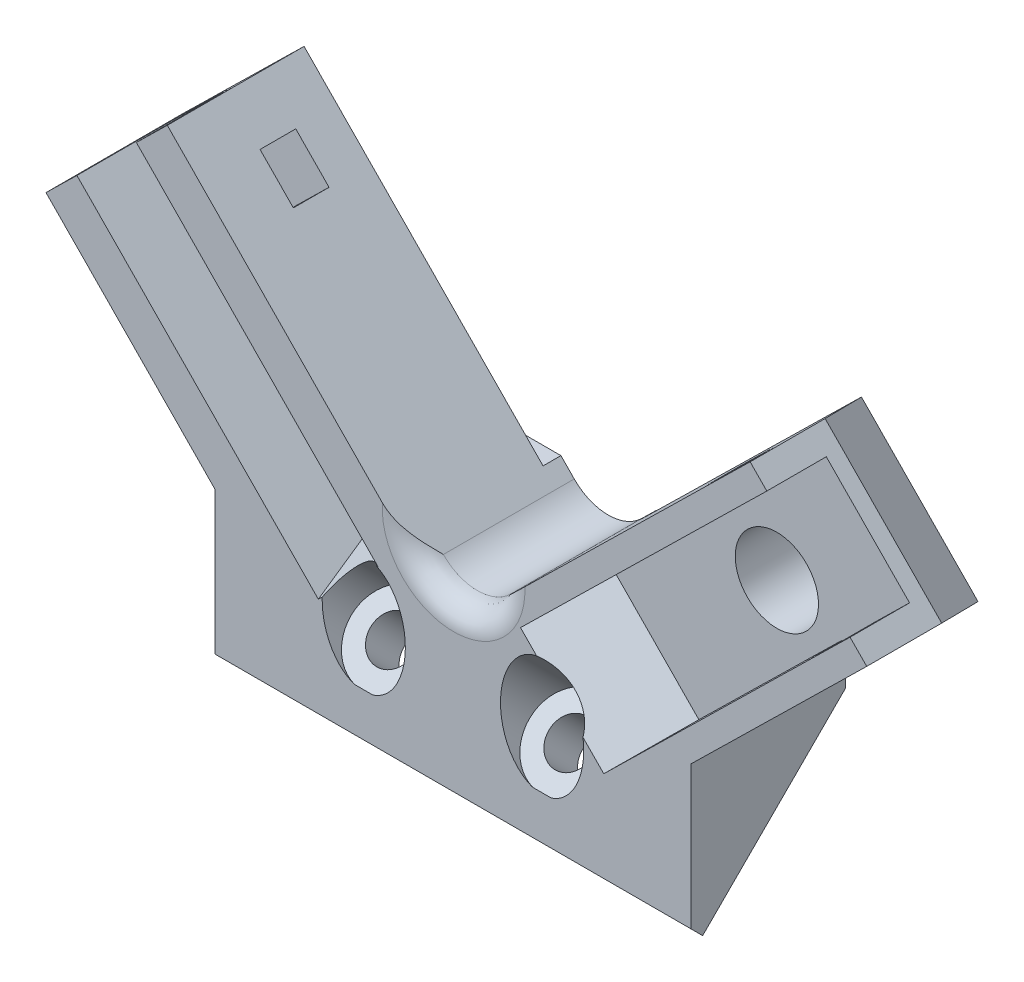
SolidWorks part; units mm, degrees
ref_plane "Plan de face" through (0, 0, 0) normal (0, 0, 1) x (1, 0, 0)
ref_plane "Plan de dessus" through (0, 0, 0) normal (0, 1, 0) x (1, 0, 0)
ref_plane "Plan de droite" through (0, 0, 0) normal (1, 0, 0) x (0, 0, -1)
sketch "Esquisse1" plane through (0, 0, 0) normal (0, 0, 1) x (1, 0, 0)
  line L0 (-20, 0) -> (20, 0)
  line L1 (20, 0) -> (20, 8)
  line L2 (20, 8) -> (34.795, 22.502)
  line L3 (34.795, 22.502) -> (24.995, 32.5)
  line L4 (24.995, 32.5) -> (0, 8)
  line L5 (0, 8) -> (-24.0148, 32.5)
  line L6 (-24.0148, 32.5) -> (-34.2148, 22.502)
  line L7 (-34.2148, 22.502) -> (-20, 8)
  line L8 (-20, 8) -> (-20, 0)
  line L9 (26.3936, 8) -> (-28.5359, 8) construction
  line L10 (0, -5.9689) -> (0, 32.3975) construction
  line L11 (-27.4321, 32.5) -> (31.9826, 32.5) construction
  line L12 (-36.6901, 22.502) -> (47.9026, 22.502) construction
  dimension "D1" = 40
  dimension "D2" = 14
  dimension "D3" = 35
  dimension "D4" = 8
extrude "Boss.-Extru.1" add sketch "Esquisse1" along normal blind 15
sketch "Esquisse2" plane through (0, 0, 15) normal (0, 0, 1) x (1, 0, 0)
  line L0 (26.395, 31.0717) -> (13.5404, 18.4717)
  line L1 (34.795, 22.502) -> (24.995, 32.5) construction
  line L2 (13.5404, 18.4717) -> (20.5404, 11.3303)
  line L3 (20.5404, 11.3303) -> (33.395, 23.9303)
  line L4 (33.395, 23.9303) -> (26.395, 31.0717)
  line L5 (26.8028, 24.47) -> (8.3585, 6.391) construction
  dimension "D1" = 18
  dimension "D2" = 10
extrude "Enlèv. mat.-Extru.1" cut sketch "Esquisse2" against normal blind 5
sketch "Esquisse3" plane through (0, 0, 15) normal (0, 0, 1) x (1, 0, 0)
  line L0 (-26.5529, 24.8874) -> (-10.8337, 8.8505) construction
  line L1 (-31.6143, 25.051) -> (-19.0143, 12.1964)
  line L2 (-19.0143, 12.1964) -> (-14.0153, 17.0964)
  line L3 (-14.0153, 17.0964) -> (-26.6153, 29.951)
  line L4 (-26.6153, 29.951) -> (-31.6143, 25.051)
  line L5 (-24.0148, 32.5) -> (-34.2148, 22.502) construction
  dimension "D1" = 7
  dimension "D2" = 18
extrude "Enlèv. mat.-Extru.2" cut sketch "Esquisse3" against normal blind 8
chamfer "Chanfrein1" distance 11 angle 50 1 edges at (17.0404, 14.901, 15) first distance on face at (0.2454, 17.8296, 15)
sketch "Esquisse8" plane through (-6.2008, -6.078, 0) normal (-0.7141, -0.7, 0) x (0, 0, 1)
  line L0 (7, 40.02) -> (7, 22.02) construction
  line L1 (7, 36.02) -> (10, 36.02)
  line L2 (7, 36.02) -> (7, 32.02)
  line L3 (7, 32.02) -> (10, 32.02)
  line L4 (10, 36.02) -> (10, 32.02)
  line L5 (15, 40.02) -> (0, 40.02) construction
  dimension "D1" = 4
  dimension "D2" = 4
  dimension "D3" = 3
extrude "Enlèv. mat.-Extru.6" cut sketch "Esquisse8" against normal blind 50
sketch "Esquisse7" plane through (5.8008, -5.918, 0) normal (0.7, -0.7141, 0) x (0.7141, 0.7, 0)
  line L0 (15.7955, 10) -> (40.6, 10) construction
  line L1 (32.6, 10) -> (36.6, 10)
  line L2 (32.6, 10) -> (32.6, 13)
  line L3 (32.6, 13) -> (36.6, 13)
  line L4 (36.6, 10) -> (36.6, 13)
  line L6 (40.6, 15) -> (40.6, 0) construction
  dimension "D1" = 4
  dimension "D2" = 4
  dimension "D3" = 3
extrude "Enlèv. mat.-Extru.5" cut sketch "Esquisse7" against normal blind 50
sketch "Esquisse6" plane through (0, 0, 0) normal (0, -1, 0) x (1, 0, 0)
  line L0 (34.795, 15) -> (34.795, 0) construction
  line L1 (-34.2148, 0) -> (34.795, 0)
  line L2 (-34.2148, 0) -> (-34.2148, 2)
  line L3 (-34.2148, 2) -> (34.795, 2)
  line L4 (34.795, 0) -> (34.795, 2)
  dimension "D1" = 2
extrude "Enlèv. mat.-Extru.4" cut sketch "Esquisse6" against normal blind 100
chamfer "Chanfrein2" distance 11 angle 70 1 edges at (-16.5148, 14.6464, 15) first distance on face at (-0.6788, 16.9237, 15)
sketch "Esquisse9" plane through (0, 0, 0) normal (0, -1, 0) x (1, 0, 0)
  line L1 (-20, 15) -> (20, 15)
  line L2 (-20, 15) -> (-20, 2)
  line L3 (-20, 2) -> (20, 2)
  line L4 (20, 15) -> (20, 2)
extrude "Boss.-Extru.2" add sketch "Esquisse9" along normal blind 5
chamfer "Chanfrein4" distance 12 angle 45 1 edges at (0, -5, 2)
sketch "Esquisse10" plane through (0, 0, 2) normal (0, 0, -1) x (-1, 0, 0)
  line L0 (-35.24, 19.9976) -> (34.76, 19.9976) construction
  line L1 (-35.24, 27.9976) -> (34.76, 27.9976) construction
  line L2 (-35.24, 27.9976) -> (-35.24, 11.9976)
  line L3 (-35.24, 11.9976) -> (34.76, 11.9976)
  line L4 (34.76, 27.9976) -> (34.76, 11.9976)
  line L5 (-29.895, 27.501) -> (-9.1098, 7.1274) construction
  line L6 (-34.795, 22.502) -> (-24.995, 32.5) construction
  line L7 (29.1148, 27.501) -> (9.1447, 7.1274) construction
  line L8 (24.0148, 32.5) -> (34.2148, 22.502) construction
  line L9 (-20, 8) -> (-34.795, 22.502) construction
  line L10 (0, 8) -> (24.0148, 32.5) construction
  line L11 (-0.24, 27.9976) -> (-0.24, 11.9976) construction
  line L13 (-35.24, 27.9976) -> (34.76, 27.9976) construction
  line L14 (-35.24, 27.9976) -> (-35.24, 37.9976)
  line L15 (-35.24, 37.9976) -> (34.76, 37.9976)
  line L16 (34.76, 27.9976) -> (34.76, 37.9976)
  circle A0 centre (-22.24, 19.9976) radius 1.75
  circle A1 centre (21.76, 19.9976) radius 1.75
  point P18 (-22.24, 19.9976)
  point P19 (21.76, 19.9976)
  dimension "D5" = 3.5
  dimension "D6" = 3.5
  dimension "D1" = 70
  dimension "D2" = 16
  dimension "D3" = 44
  dimension "D4" = 10
extrude "Enlèv. mat.-Extru.7" cut sketch "Esquisse10" against normal blind 1.5
chamfer "Chanfrein5" distance 3 angle 60 1 edges at (29.895, 27.501, 3.5) first distance on face at (20.49, 19.9976, 3.5)
sketch "Esquisse11" plane through (0, 0, 2) normal (0, 0, -1) x (-1, 0, 0)
  circle A0 centre (-22.24, 19.9976) radius 1.75
  circle A1 centre (21.76, 19.9976) radius 1.75
  dimension "D1" = 3.5
  dimension "D2" = 3.5
extrude "Enlèv. mat.-Extru.8" cut sketch "Esquisse11" against normal through all
sketch "Esquisse12" plane through (0, 0, 7) normal (0, 0, 1) x (1, 0, 0)
  circle A0 centre (-21.76, 19.9976) radius 3.5
  dimension "D1" = 7
extrude "Enlèv. mat.-Extru.9" cut sketch "Esquisse12" against normal blind 2.5
sketch "Esquisse13" plane through (0, 0, 10) normal (0, 0, 1) x (1, 0, 0)
  circle A0 centre (22.24, 19.9976) radius 3.5
  dimension "D1" = 7
extrude "Enlèv. mat.-Extru.10" cut sketch "Esquisse13" against normal blind 5.5
fillet "Congé1" radius 4 1 edges at (0, 8, 8.5)
chamfer "Chanfrein10" distance 1 angle 45 1 edges at (0, -5, 15)
sketch "Esquisse14" plane through (0, 4.5, 4.5) normal (0, -0.7071, -0.7071) x (1, 0, 0)
  line L0 (-13.9188, 7.435) -> (13.5231, 7.435) construction
  line L1 (0, 0) -> (0, 16.2802) construction
  line L2 (-20, 13.435) -> (20, 13.435) construction
  circle A0 centre (-7.5, 7.435) radius 1.85
  circle A1 centre (7.5, 7.435) radius 1.85
  dimension "D1" = 3.7
  dimension "D2" = 3.7
  dimension "D3" = 15
  dimension "D4" = 6
extrude "Enlèv. mat.-Extru.11" cut sketch "Esquisse14" against normal through all
sketch "Esquisse15" plane through (0, 4.5, 4.5) normal (0, -0.7071, -0.7071) x (1, 0, 0)
  circle A0 centre (-7.5, 7.435) radius 3.5
  circle A1 centre (7.5, 7.435) radius 3.5
  dimension "D1" = 7
  dimension "D2" = 7
extrude "Enlèv. mat.-Extru.12" cut sketch "Esquisse15" against normal through all from offset 4 offset against normal yes
fillet "Congé2" radius 2 1 edges at (0.0166, 9.6568, 15) tangent propagation no
